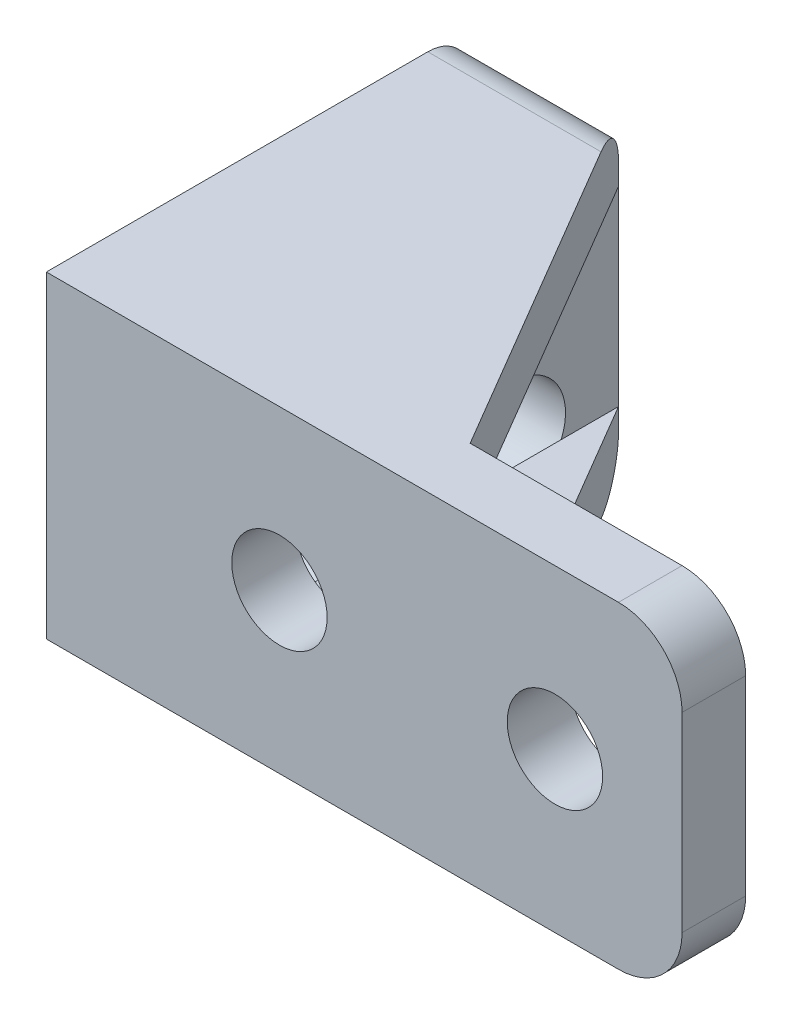
SolidWorks part; units mm, degrees
ref_plane "Front Plane" through (0, 0, 0) normal (0, 0, 1) x (1, 0, 0)
ref_plane "Top Plane" through (0, 0, 0) normal (0, 1, 0) x (1, 0, 0)
ref_plane "Right Plane" through (0, 0, 0) normal (1, 0, 0) x (0, 0, -1)
sketch "Sketch1" plane through (0, 0, 0) normal (0, 1, 0) x (1, 0, 0)
  line L1 (15, -1.5) -> (-15, -1.5)
  line L2 (15, -1.5) -> (15, 1.5)
  line L3 (15, 1.5) -> (-15, 1.5)
  line L4 (-15, -1.5) -> (-15, 1.5)
  line L5 (15, -1.5) -> (-15, 1.5) construction
  line L6 (15, 1.5) -> (-15, -1.5) construction
  line L7 (-15, 1.5) -> (-8, 1.5)
  line L8 (-15, 1.5) -> (-15, 18.5)
  line L9 (-15, 18.5) -> (-8, 18.5)
  line L10 (-8, 1.5) -> (-8, 18.5)
  point P0 (0, 0)
  dimension "D1" = 30
  dimension "D2" = 3
  dimension "D3" = 7
  dimension "D4" = 17
extrude "Boss-Extrude1" add sketch "Sketch1" along normal blind 15 contours L4 L1 L2 L3 | L3 L10 L9 L8 region at (0, 0, 0) region at (-11.5, 0, -10)
sketch "Sketch3" plane through (0, 15, 0) normal (0, 1, 0) x (1, 0, 0)
  line L0 (-8, 18.5) -> (2, 1.5)
  line L1 (15, 1.5) -> (-8, 1.5) construction
  line L2 (-8, 18.5) -> (-8, 1.5)
  line L3 (-8, 1.5) -> (2, 1.5)
  dimension "D1" = 10
extrude "Boss-Extrude2" add sketch "Sketch3" against normal blind 3 contours L0 L3 L2
extrude "Boss-Extrude3" add sketch "Sketch3<3>" along normal blind 3 from surface starting at face at (-2.6667, 0, -6.1667)
sketch "Sketch3<3>" plane through (0, 15, 0) normal (0, 1, 0) x (1, 0, 0) same geometry as "Sketch3"
sketch "Sketch4" plane through (-15, 0, 0) normal (-1, 0, 0) x (0, 0, 1)
  line L0 (1.5, 15) -> (1.5, 0) construction
  line L1 (1.5, 15) -> (-18.5, 15) construction
  line L2 (1.5, 0) -> (-18.5, 0) construction
  circle A0 centre (-3.5, 11) radius 2.5
  circle A1 centre (-13.5, 11) radius 2.5
  circle A2 centre (-3.5, 4) radius 2.5
  circle A3 centre (-13.5, 4) radius 2.5
  point P12 (0, 0)
  point P13 (0, 0)
  point P14 (0, 0)
  dimension "D2" = 5
  dimension "D1" = 5
  dimension "D3" = 10
  dimension "D4" = 4
  dimension "D5" = 4
extrude "Cut-Extrude1" cut sketch "Sketch4" against normal up to surface (7 mm away) up to face at (-8, 7.5, -10)
sketch "Sketch5" plane through (0, 0, -1.5) normal (0, 0, -1) x (-1, 0, 0)
  line L0 (-15, 7.5) -> (15, 7.5) construction
  line L1 (-15, 15) -> (-15, 0) construction
  line L2 (15, 15) -> (15, 0) construction
  circle A0 centre (-9, 7.5) radius 2.25
  circle A1 centre (4, 7.5) radius 2.25
  point P10 (0, 0)
  point P11 (0, 0)
  dimension "D1" = 4.5
  dimension "D2" = 6
  dimension "D3" = 13
extrude "Cut-Extrude2" cut sketch "Sketch5" against normal blind 7
fillet "Fillet3" radius 3 2 edges at (15, 15, 0) (15, 0, 0)
fillet "Fillet4" radius 2 2 edges at (-11.5, 15, -18.5) (-11.5, 0, -18.5)
